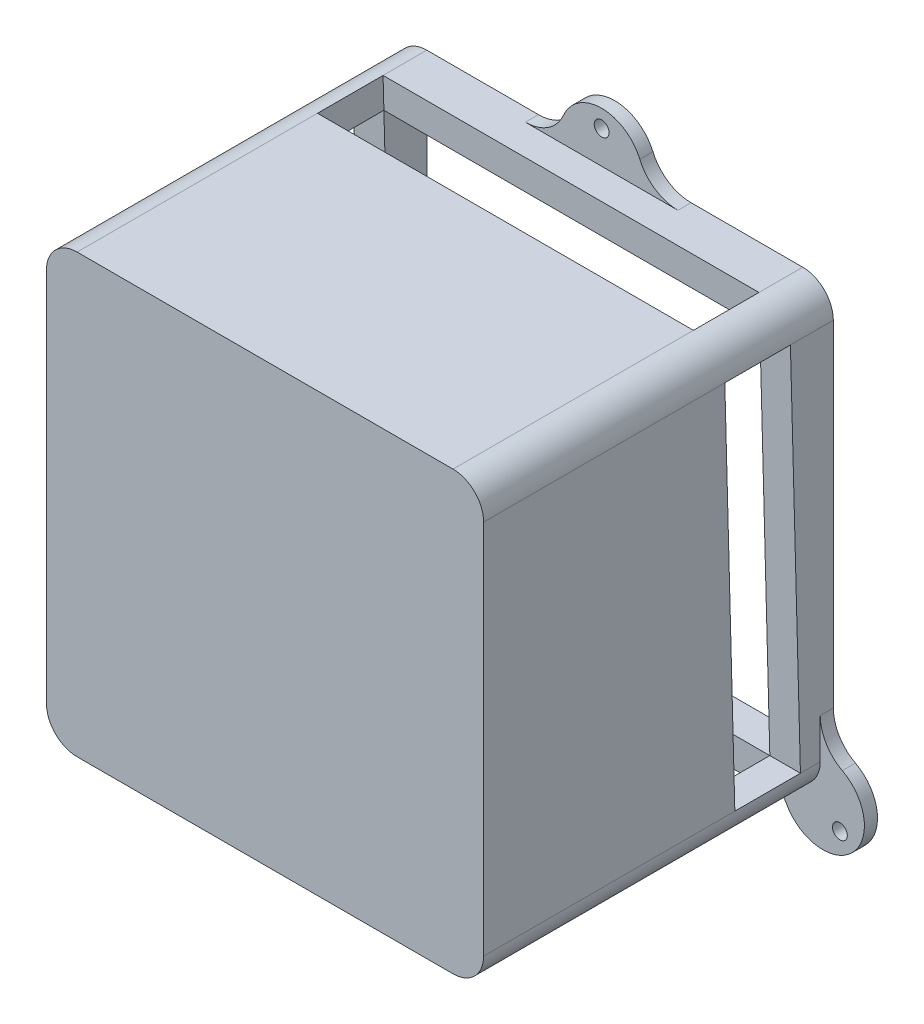
SolidWorks part; units mm, degrees
ref_plane "Plan de face" through (0, 0, 0) normal (0, 0, 1) x (1, 0, 0)
ref_plane "Plan de dessus" through (0, 0, 0) normal (0, 1, 0) x (1, 0, 0)
ref_plane "Plan de droite" through (0, 0, 0) normal (1, 0, 0) x (0, 0, -1)
sketch "Esquisse1" plane through (0, 0, 0) normal (0, 0, 1) x (1, 0, 0)
  line L1 (0, 0) -> (100, 0)
  line L2 (0, 0) -> (0, 100)
  line L3 (0, 100) -> (100, 100)
  line L4 (100, 0) -> (100, 100)
  dimension "D1" = 100
  dimension "D2" = 100
extrude "Boss.-Extru.1" add sketch "Esquisse1" along normal blind 80
sketch "Esquisse2" plane through (0, 0, 0) normal (0, 0, -1) x (-1, 0, 0)
  line L8 (-7, 7) -> (-7, 93)
  line L9 (-7, 93) -> (-93, 93)
  line L10 (-93, 93) -> (-93, 7)
  line L11 (-93, 7) -> (-7, 7)
  line L12 (-7, 7) -> (-7, 93)
  line L13 (-7, 93) -> (-93, 93)
  line L14 (-93, 93) -> (-93, 7)
  line L15 (-93, 7) -> (-7, 7)
  dimension "D1" = 7
extrude "Enlèv. mat.-Extru.1" cut sketch "Esquisse2" against normal offset from surface (70 mm away) 10 up to face at (50, 50, 80)
sketch "Esquisse3" plane through (0, 0, 80) normal (0, 0, 1) x (1, 0, 0)
  line L0 (95, 95) -> (5, 95)
  line L1 (5, 95) -> (5, 5)
  line L2 (5, 5) -> (95, 5)
  line L3 (95, 5) -> (95, 95)
  line L4 (0, 100) -> (0, 0)
  line L5 (0, 0) -> (100, 0)
  line L6 (100, 0) -> (100, 100)
  line L7 (100, 100) -> (0, 100)
  line L8 (0, 100) -> (0, 0)
  line L9 (0, 0) -> (100, 0)
  line L10 (100, 0) -> (100, 100)
  line L11 (100, 100) -> (0, 100)
  dimension "D1" = 0
  dimension "D2" = 5
extrude "Boss.-Extru.2" [suppressed] add sketch "Esquisse3" along normal blind 10
sketch "Esquisse4" plane through (0, 0, 0) normal (0, 0, -1) x (-1, 0, 0)
  line L0 (-93, 7) -> (-116.2207, -16.2207) construction
  line L1 (-7, 7) -> (8.1122, -8.1122) construction
  line L6 (0, 0) -> (-100, 0) construction
  line L7 (3.2972, -11.3596) -> (13.4788, -1.1781) construction
  line L8 (-114.7245, 0.0676) -> (-101.0769, -13.5799) construction
  line L9 (-50, 93) -> (-50, 115.4924) construction
  line L10 (-7, 93) -> (-93, 93) construction
  line L11 (-100, 100) -> (0, 100) construction
  line L12 (-62.0341, 111.5) -> (-40.7837, 111.5) construction
  line L13 (-46.9586, 93) -> (-53.0414, 93)
  circle A0 centre (-104.5, -4.5) radius 1.5
  circle A1 centre (4.5, -4.5) radius 1.5
  circle A2 centre (0.6109, -0.6109) radius 9.5
  circle A3 centre (-100.6109, -0.6109) radius 9.5
  circle A4 centre (-50, 107.5) radius 1.5
  arc A5 (-46.9586, 93) -> (-53.0414, 93) centre (-50, 102) ccw
  point P28 (-50, 100)
  dimension "D1" = 3
  dimension "D4" = 3
  dimension "D7" = 19
  dimension "D8" = 19
  dimension "D10" = 3
  dimension "D12" = 19
  dimension "D2" = 4.5
  dimension "D3" = 4
  dimension "D5" = 4.5
  dimension "D6" = 4
  dimension "D9" = 7.5
  dimension "D11" = 4
extrude "Boss.-Extru.3" add sketch "Esquisse4" against normal blind 3
fillet "Congé1" radius 7 4 edges at (100, 0, 41.5) (0, 100, 40) (0, 0, 41.5) (100, 100, 40)
fillet "Congé3" [suppressed] radius 1 type face fillet
fillet "Congé4" radius 9.5 6 edges at (8.8694, 0, 1.5) (0, 8.8694, 1.5) (91.1306, 0, 1.5) (100, 8.8694, 1.5) (59.2871, 100, 1.5) (40.7129, 100, 1.5)
hole_wizard "Dégagement M31" positions "Esquisse5" profile "Esquisse6" hole size "M3" standard "ISO" end condition up to next
sketch "Esquisse5" plane through (0, 0, 3) normal (0, 0, 1) x (1, 0, 0)
  point P0 (104.5, -4.5)
  point P3 (-4.5, -4.5)
  point P6 (50, 107.5)
sketch "Esquisse6" plane through (104.5, -4.5, 3) normal (1, 0, 0) x (0, -1, 0)
  line L0 (0, 0) -> (0, 3)
  line L1 (0, 3) -> (1.7, 3)
  line L2 (1.7, 3) -> (1.7, 0)
  line L5 (1.7, 0) -> (0, 0)
  line L11 (0, -6.35) -> (0, 107.95) construction
  dimension "Diamètre du perçage jusqu'au prochain" = 3.4
  dimension "Profondeur du perçage jusqu'au prochain" = 3
ref_plane "Plan1" through (0, 100, 0) normal (0, 1, 0) x (1, 0, 0)
ref_plane "Plan2" through (0, 102.0609, 2.7218) normal (0, 0.9996, 0.0267) x (1, 0, 0)
sketch "Esquisse8" plane through (0, 102.0609, 2.7218) normal (0, 0.9996, 0.0267) x (1, 0, 0)
  line L0 (7, 2.6658) -> (7, -77.3057) construction
  line L1 (7, -22.3342) -> (93, -22.3342)
  line L2 (7, -22.3342) -> (7, -7.3342)
  line L3 (7, -7.3342) -> (93, -7.3342)
  line L4 (93, -22.3342) -> (93, -7.3342)
  line L5 (93, -77.3057) -> (93, 2.6658) construction
  line L6 (0, 2.6658) -> (100, 2.6658) construction
  dimension "D1" = 15
  dimension "D2" = 10
extrude "Enlèv. mat.-Extru.2" cut sketch "Esquisse8" against normal up to surface (101.5015 mm away) up to face at (50, 0, 21.5)
sketch "Esquisse9" plane through (93, 0, 0) normal (-1, 0, 0) x (0, 0, 1)
  line L0 (24.8222, 93) -> (22.5288, 7)
  line L1 (22.5288, 7) -> (7.5234, 7)
  line L2 (7.5234, 7) -> (9.8169, 93)
  line L3 (9.8169, 93) -> (24.8222, 93)
extrude "Enlèv. mat.-Extru.3" cut sketch "Esquisse9" along normal up to surface (93 mm away) from surface up to face at (0, 38.7272, 27.6667) starting at face at (100, 38.7272, 27.6667)
